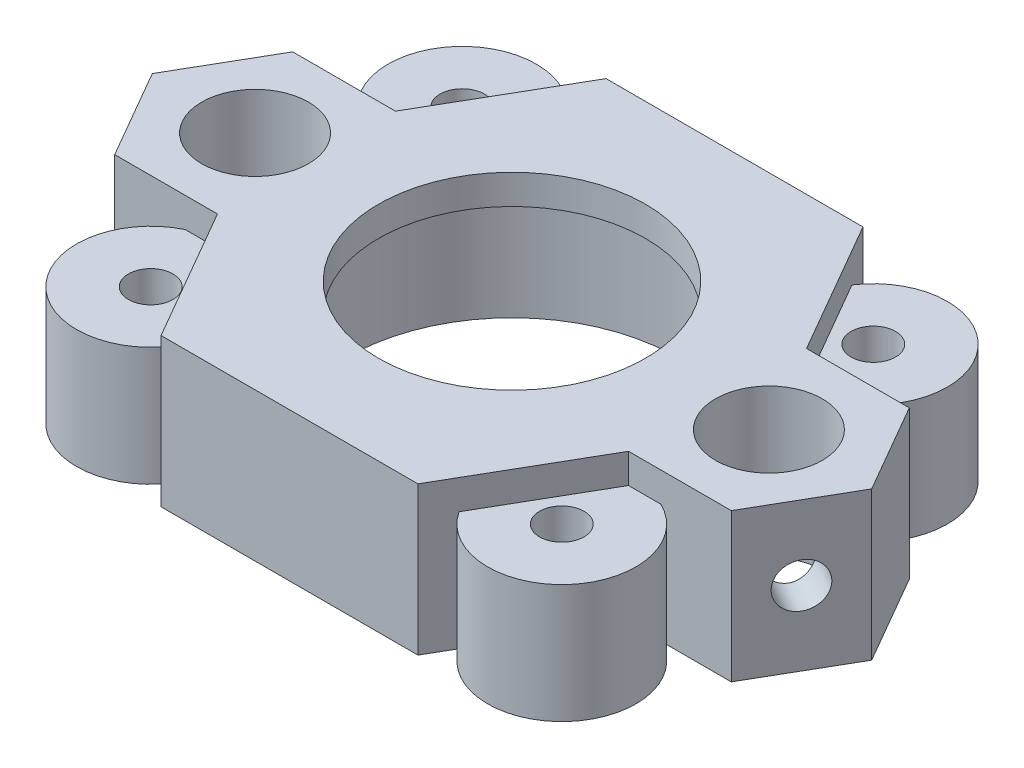
SolidWorks part; units mm, degrees
ref_plane "Front Plane" through (0, 0, 0) normal (0, 0, 1) x (1, 0, 0)
ref_plane "Top Plane" through (0, 0, 0) normal (0, 1, 0) x (1, 0, 0)
ref_plane "Right Plane" through (0, 0, 0) normal (1, 0, 0) x (0, 0, -1)
sketch "Sketch1" plane through (0, 0, 0) normal (0, 1, 0) x (1, 0, 0)
  line L0 (0, 0) -> (17.3205, 0) construction
  line L1 (17.3205, 0) -> (15.5205, 3.1177) construction
  line L2 (8.6603, 15) -> (-8.6603, 15)
  line L3 (-8.6603, 15) -> (-9.6753, 13.2419)
  line L4 (-9.6753, -13.2419) -> (-8.6603, -15)
  line L5 (-8.6603, -15) -> (8.6603, -15)
  line L6 (8.6603, -15) -> (9.6753, -13.2419)
  line L7 (0, 15) -> (0, -15) construction
  line L8 (24.2487, 0) -> (20.7846, 6)
  line L9 (20.7846, 6) -> (16.0359, 6)
  line L10 (12.1244, 3) -> (11.064, 1.1634)
  line L11 (11.064, -1.1634) -> (12.1244, -3) construction
  line L12 (16.0359, -6) -> (20.7846, -6)
  line L13 (20.7846, -6) -> (24.2487, 0)
  line L14 (-20.7846, -6) -> (-24.2487, 0)
  line L15 (-16.0359, -6) -> (-20.7846, -6)
  line L16 (-11.064, -1.1634) -> (-13.8564, -6) construction
  line L17 (-13.8564, 6) -> (-11.064, 1.1634) construction
  line L18 (-20.7846, 6) -> (-16.0359, 6)
  line L19 (-24.2487, 0) -> (-20.7846, 6)
  line L20 (-13.8564, 6) -> (-15.5205, 3.1177) construction
  line L21 (-15.5205, 3.1177) -> (-17.3205, 0) construction
  line L22 (-17.3205, 0) -> (-15.5205, -3.1177) construction
  line L23 (-11.064, 1.1634) -> (-10.3923, 0) construction
  line L24 (-10.3923, 0) -> (-11.064, -1.1634) construction
  line L25 (-15.5205, -3.1177) -> (-13.8564, -6) construction
  line L26 (11.064, 1.1634) -> (10.3923, 0) construction
  line L27 (10.3923, 0) -> (11.064, -1.1634) construction
  line L28 (12.1244, -3) -> (13.8564, -6) construction
  line L29 (15.5205, 3.1177) -> (14.3205, 5.1962) construction
  line L30 (9.6753, 13.2419) -> (8.6603, 15)
  line L31 (14.3205, -5.1962) -> (15.5205, -3.1177) construction
  line L32 (15.5205, -3.1177) -> (17.3205, 0) construction
  line L33 (13.8564, -6) -> (14.3205, -5.1962) construction
  line L34 (13.8564, 6) -> (12.1244, 3) construction
  line L35 (14.3205, 5.1962) -> (13.8564, 6) construction
  line L36 (-13.8564, 6) -> (-13.8564, 15) construction
  line L37 (-13.8564, 15) -> (-8.6603, 15) construction
  line L38 (-9.6753, 13.2419) -> (-13.8564, 6) construction
  line L39 (-16.0359, 6) -> (-13.8564, 6) construction
  line L40 (-55, 0) -> (55, 0) construction
  line L41 (-13.8564, -6) -> (-9.6753, -13.2419) construction
  line L42 (-13.8564, -6) -> (-16.0359, -6) construction
  line L43 (9.6753, -13.2419) -> (13.8564, -6) construction
  line L44 (13.8564, -6) -> (16.0359, -6) construction
  line L45 (16.0359, 6) -> (13.8564, 6) construction
  line L46 (13.8564, 6) -> (9.6753, 13.2419) construction
  line L47 (-17.3205, 0) -> (-8.6603, 15)
  circle A0 centre (0, 0) radius 11.125
  circle A1 centre (0, 0) radius 15 construction
  circle A2 centre (17.3205, 0) radius 3.6
  circle A3 centre (17.3205, 0) radius 6 construction
  circle A4 centre (-17.3205, 0) radius 3.6
  arc A5 (-9.6753, 13.2419) -> (-16.0359, 6) centre (-13.8564, 10.5) ccw
  circle A6 centre (-13.8564, 10.5) radius 1.5
  arc A7 (-13.5724, 5.5081) -> (-9.0703, 11.9469) centre (-13.8564, 10.5) ccw construction
  arc A8 (-9.0703, 11.9469) -> (-9.6753, 13.2419) centre (-13.8564, 10.5) ccw construction
  arc A9 (-13.9549, 5.501) -> (-13.5724, 5.5081) centre (-13.8564, 10.5) ccw construction
  arc A10 (-14.1404, 5.5081) -> (-13.9549, 5.501) centre (-13.8564, 10.5) ccw construction
  arc A11 (-16.0359, 6) -> (-14.1404, 5.5081) centre (-13.8564, 10.5) ccw construction
  circle A12 centre (13.8564, 10.5) radius 1.5
  arc A13 (9.6753, 13.2419) -> (16.0359, 6) centre (13.8564, 10.5) cw
  circle A14 centre (13.8564, -10.5) radius 1.5
  arc A15 (9.6753, -13.2419) -> (16.0359, -6) centre (13.8564, -10.5) ccw
  circle A16 centre (-13.8564, -10.5) radius 1.5
  arc A17 (-9.6753, -13.2419) -> (-16.0359, -6) centre (-13.8564, -10.5) cw
  dimension "D1" = 22.25
  dimension "D3" = 7.2
  dimension "D6" = 10
  dimension "D7" = 3
  dimension "D2" = 30
  dimension "D4" = 12
  dimension "D5" = 90
extrude "Boss-Extrude1" add sketch "Sketch1" along normal blind 8 contours A6 | A12 | A14 | A16 | L30 L2 L3 A5 L18 L19 L14 L15 A17 L4 L5 L6 A15 L12 L13 L8 L9 A13 | A0 | A4 | A2 region at (-13.8564, 0, -10.5) region at (13.8564, 0, -10.5) region at (13.8564, 0, 10.5) region at (-13.8564, 0, 10.5)
sketch "Sketch2" plane through (0, 8, 0) normal (0, 1, 0) x (1, 0, 0)
  line L1 (8.6603, -15) -> (13.8564, -6)
  line L2 (17.3205, 0) -> (15.5205, 3.1177) construction
  line L3 (8.6603, 15) -> (-8.6603, 15)
  line L4 (-8.6603, 15) -> (-13.8564, 6)
  line L5 (-13.8564, -6) -> (-8.6603, -15)
  line L6 (-8.6603, -15) -> (8.6603, -15)
  line L8 (20.7846, -6) -> (24.2487, 0)
  line L9 (24.2487, 0) -> (20.7846, 6)
  line L10 (20.7846, 6) -> (13.8564, 6)
  line L11 (13.8564, 6) -> (13.7942, 5.8923) construction
  line L12 (10.3923, 0) -> (12.1244, -3) construction
  line L13 (13.8564, -6) -> (20.7846, -6)
  line L15 (-20.7846, -6) -> (-13.8564, -6)
  line L16 (-13.8564, -6) -> (-13.7942, -5.8923) construction
  line L17 (-10.3923, 0) -> (-12.1244, 3) construction
  line L18 (-13.8564, 6) -> (-20.7846, 6)
  line L19 (-20.7846, 6) -> (-24.2487, 0)
  line L20 (-24.2487, 0) -> (-20.7846, -6)
  line L21 (16.0359, -6) -> (20.7846, -6) construction
  line L22 (-16.0359, -6) -> (-20.7846, -6) construction
  line L23 (-14.3205, 5.1962) -> (-15.5205, 3.1177) construction
  line L24 (-15.5205, 3.1177) -> (-17.3205, 0) construction
  line L25 (-17.3205, 0) -> (-15.5205, -3.1177) construction
  line L26 (-15.5205, -3.1177) -> (-14.3205, -5.1962) construction
  line L27 (-14.3205, -5.1962) -> (-13.8564, -6) construction
  line L28 (-13.8564, 6) -> (-14.3205, 5.1962) construction
  line L29 (-12.1244, 3) -> (-13.7942, 5.8923) construction
  line L30 (-13.7942, 5.8923) -> (-13.8564, 6) construction
  line L31 (-12.1244, -3) -> (-10.3923, 0) construction
  line L32 (-13.7942, -5.8923) -> (-12.1244, -3) construction
  line L33 (15.5205, 3.1177) -> (14.3205, 5.1962) construction
  line L34 (13.8564, 6) -> (8.6603, 15)
  line L35 (15.5205, -3.1177) -> (17.3205, 0) construction
  line L36 (14.3205, -5.1962) -> (15.5205, -3.1177) construction
  line L37 (13.8564, -6) -> (14.3205, -5.1962) construction
  line L38 (12.1244, -3) -> (13.7942, -5.8923) construction
  line L39 (13.7942, -5.8923) -> (13.8564, -6) construction
  line L40 (12.1244, 3) -> (10.3923, 0) construction
  line L41 (13.7942, 5.8923) -> (12.1244, 3) construction
  line L42 (14.3205, 5.1962) -> (13.8564, 6) construction
  circle A0 centre (0, 0) radius 9
  circle A1 centre (-17.3205, 0) radius 3.6
  circle A2 centre (17.3205, 0) radius 3.6
  arc A3 (-13.7942, -5.8923) -> (14.1162, 5.0727) centre (0, 0) ccw construction
  circle A4 centre (17.3205, 0) radius 6 construction
  circle A5 centre (-17.3205, 0) radius 3.6 construction
  circle A6 centre (17.3205, 0) radius 3.6 construction
  arc A7 (-14.1162, 5.0727) -> (-14.1162, -5.0727) centre (-17.3205, 0) ccw construction
  arc A8 (-14.1162, -5.0727) -> (-13.7942, -5.8923) centre (0, 0) ccw construction
  arc A9 (-13.7942, 5.8923) -> (-14.1162, 5.0727) centre (0, 0) ccw construction
  arc A10 (-14.1162, 5.0727) -> (-14.1162, -5.0727) centre (0, 0) ccw construction
  arc A11 (-12.1244, 3) -> (-14.1162, 5.0727) centre (-17.3205, 0) ccw construction
  arc A12 (-14.1162, -5.0727) -> (-12.1244, -3) centre (-17.3205, 0) ccw construction
  arc A13 (-12.1244, -3) -> (-12.1244, 3) centre (-17.3205, 0) ccw construction
  arc A14 (14.1162, 5.0727) -> (13.7942, 5.8923) centre (0, 0) ccw construction
  arc A15 (13.7942, 5.8923) -> (-13.7942, 5.8923) centre (0, 0) ccw construction
  dimension "D1" = 18
extrude "Boss-Extrude2" add sketch "Sketch2" along normal blind 2
sketch "Sketch4" plane through (-18.1865, 0, 10.5) normal (-0.866, 0, 0.5) x (0.5, 0, 0.866)
  line L0 (-8.6603, 10) -> (-8.6603, 0) construction
  line L2 (-12.1244, 10) -> (-12.1244, 0) construction
  line L3 (-12.1244, 5) -> (-5.1962, 5) construction
  line L5 (-5.1962, 10) -> (-5.1962, 0) construction
  line L7 (-12.1244, 10) -> (-5.1962, 10) construction
  circle A0 centre (-8.6603, 5) radius 1.5
  dimension "D1" = 3
extrude "Cut-Extrude1" cut sketch "Sketch4" against normal up to surface and the other way through all up to face at (-17.3205, 0, -3.6)
sketch "Sketch5" plane through (18.1865, 0, 10.5) normal (0.866, 0, 0.5) x (0.5, 0, -0.866)
  line L0 (8.6603, 10) -> (8.6603, 0) construction
  line L2 (5.1962, 10) -> (5.1962, 0) construction
  line L3 (5.1962, 5) -> (12.1244, 5) construction
  line L6 (5.1962, 0) -> (12.1244, 0) construction
  circle A0 centre (8.6603, 5) radius 1.5
  dimension "D1" = 3
extrude "Cut-Extrude2" cut sketch "Sketch5" against normal up to surface (2.7274 mm away) up to face at (17.3205, 0, 3.6)
